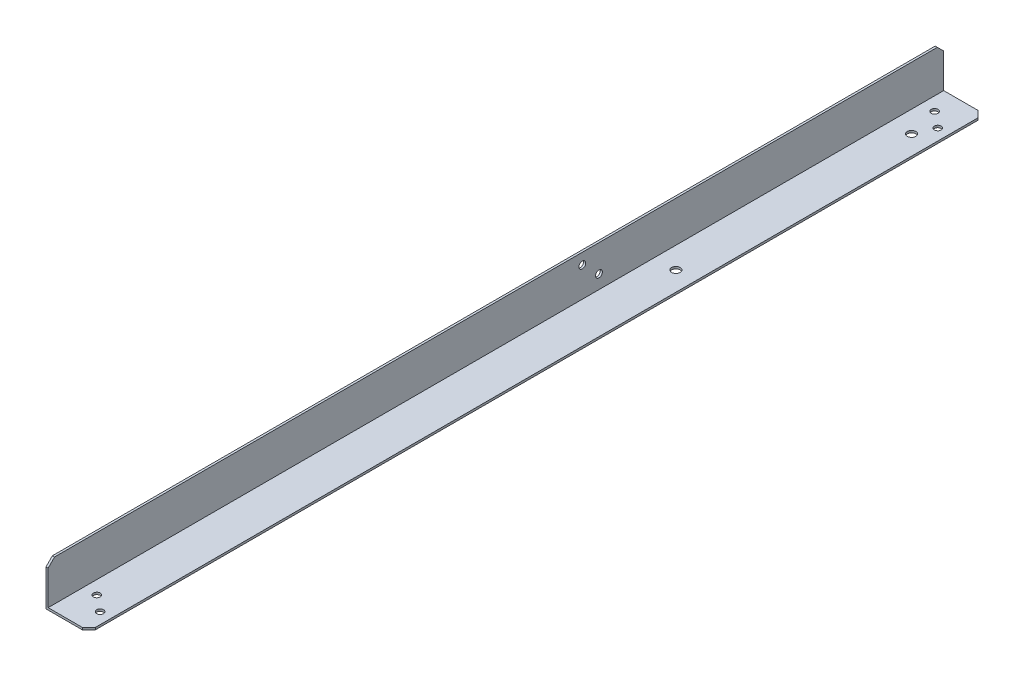
SolidWorks part; units mm, degrees
material "6063-T5"
ref_plane "Спереди" through (0, 0, 0) normal (0, 0, 1) x (1, 0, 0)
ref_plane "Сверху" through (0, 0, 0) normal (0, 1, 0) x (1, 0, 0)
ref_plane "Справа" through (0, 0, 0) normal (1, 0, 0) x (0, 0, -1)
sketch "Sketch1" plane through (0, 0, 0) normal (0, 0, 1) x (1, 0, 0)
  line L0 (0, 0) -> (20, 0)
  line L1 (20, 0) -> (20, 1)
  line L2 (20, 1) -> (1, 1)
  line L3 (1, 1) -> (1, 20)
  line L4 (1, 20) -> (0, 20)
  line L5 (0, 20) -> (0, 0)
  dimension "D1" = 20
  dimension "D2" = 20
  dimension "D4" = 1
extrude "Base" add sketch "Sketch1" along normal blind 418
chamfer "Chamfer1" distance 3 angle 45 4 edges at (20, 0.5, 418) (0.5, 20, 418) (0.5, 20, 0) (20, 0.5, 0)
hole_wizard "Ø3.2 (3.2) Cable Carrier Holes" positions "Sketch6" profile "Sketch7" hole size "Ø3.2" standard "ANSI Metric" end condition through all
sketch "Sketch6" plane through (1, 0, 0) normal (1, 0, 0) x (0, 0, -1)
  line L0 (-415, 0) -> (-3, 0) construction
  line L1 (0, 1) -> (0, 17) construction
  point P0 (-168.7, 14.85)
  point P2 (-160.9, 7.35)
  dimension "D1" = 7.5
  dimension "D2" = 7.8
  dimension "D3" = 7.35
  dimension "D4" = 168.7
sketch "Sketch7" plane through (1, 14.85, 168.7) normal (0, 1, 0) x (0, 0, -1)
  line L0 (0, 0) -> (0, 1)
  line L1 (0, 1) -> (1.6, 1)
  line L2 (1.6, 1) -> (1.6, 0)
  line L5 (1.6, 0) -> (0, 0)
  line L11 (0, -6.35) -> (0, 107.95) construction
  dimension "Thru Hole Dia." = 3.2
  dimension "Thru Hole Depth" = 1
hole_wizard "Ø3.2 (3.2) Diameter Hole2" positions "Sketch8" profile "Sketch9" hole size "Ø3.2" standard "ANSI Metric" end condition through all
sketch "Sketch8" plane through (0, 1, 0) normal (0, 1, 0) x (1, 0, 0)
  line L0 (0, -415) -> (0, -3) construction
  line L2 (17, -418) -> (1, -418) construction
  line L3 (17, 0) -> (1, 0) construction
  point P0 (7.25, -401.5)
  point P2 (14.75, -407.5)
  point P4 (7.25, -10.5)
  point P6 (14.75, -16.5)
  dimension "D1" = 6
  dimension "D2" = 6
  dimension "D3" = 7.5
  dimension "D4" = 7.25
  dimension "D5" = 10.5
  dimension "D6" = 10.5
sketch "Sketch9" plane through (7.25, 1, 401.5) normal (1, 0, 0) x (0, 0, 1)
  line L0 (0, 0) -> (0, 1)
  line L1 (0, 1) -> (1.6, 1)
  line L2 (1.6, 1) -> (1.6, 0)
  line L5 (1.6, 0) -> (0, 0)
  line L11 (0, -6.35) -> (0, 107.95) construction
  dimension "Thru Hole Dia." = 3.2
  dimension "Thru Hole Depth" = 1
hole_wizard "Ø4.0 (4) Cable Tie Holes" positions "Sketch10" profile "Sketch11" hole size "Ø4.0" standard "ANSI Metric" end condition through all
sketch "Sketch10" plane through (0, 1, 0) normal (0, 1, 0) x (1, 0, 0)
  line L0 (0, -415) -> (0, -3) construction
  line L1 (17, 0) -> (1, 0) construction
  point P0 (11, -25)
  point P2 (11, -135)
  dimension "D1" = 11
  dimension "D2" = 25
  dimension "D3" = 135
sketch "Sketch11" plane through (11, 1, 25) normal (1, 0, 0) x (0, 0, 1)
  line L0 (0, 0) -> (0, 1)
  line L1 (0, 1) -> (2, 1)
  line L2 (2, 1) -> (2, 0)
  line L5 (2, 0) -> (0, 0)
  line L11 (0, -6.35) -> (0, 107.95) construction
  dimension "Thru Hole Dia." = 4
  dimension "Thru Hole Depth" = 1
equation "\"D1@Sketch1\"=\"D2@Sketch1\""
